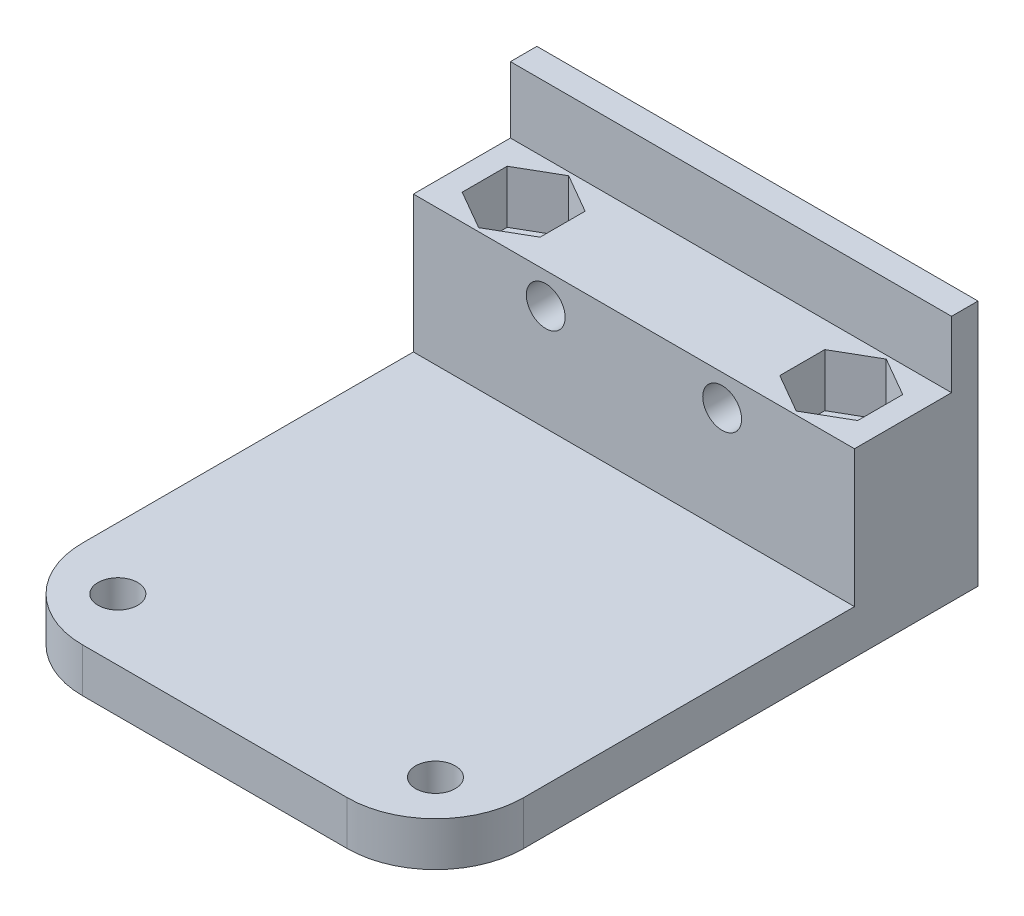
SolidWorks part; units mm, degrees
ref_plane "Front Plane" through (0, 0, 0) normal (0, 0, 1) x (1, 0, 0)
ref_plane "Top Plane" through (0, 0, 0) normal (0, 1, 0) x (1, 0, 0)
ref_plane "Right Plane" through (0, 0, 0) normal (1, 0, 0) x (0, 0, -1)
sketch "Sketch1" plane through (0, 0, 0) normal (0, 0, 1) x (1, 0, 0)
  line L1 (-25, 16.5) -> (25, 16.5)
  line L2 (-25, 16.5) -> (-25, -16.5)
  line L3 (-25, -16.5) -> (25, -16.5)
  line L4 (25, 16.5) -> (25, -16.5)
  line L5 (-25, 16.5) -> (25, -16.5) construction
  line L6 (-25, -16.5) -> (25, 16.5) construction
  point P0 (0, 0)
  dimension "D1" = 33
  dimension "D2" = 50
extrude "Boss-Extrude1" add sketch "Sketch1" along normal blind 3 contours L2 L3 L4 L1
sketch "Sketch2" plane through (0, 0, 3) normal (0, 0, 1) x (1, 0, 0)
  line L0 (25, 16.5) -> (25, -16.5) construction
  line L1 (-25, -16.5) -> (25, -16.5)
  line L2 (-25, -16.5) -> (-25, -11.5)
  line L3 (-25, -11.5) -> (25, -11.5)
  line L4 (25, -16.5) -> (25, -11.5)
  dimension "D1" = 5
extrude "Boss-Extrude2" add sketch "Sketch2" along normal blind 58.5
sketch "Sketch6" plane through (0, 0, 3) normal (0, 0, 1) x (1, 0, 0)
  line L0 (25, 16.5) -> (25, -11.5) construction
  line L1 (-25, 16.5) -> (25, 16.5)
  line L2 (-25, 16.5) -> (-25, 11.5)
  line L3 (-25, 11.5) -> (25, 11.5)
  line L4 (25, 16.5) -> (25, 11.5)
  dimension "D1" = 5
extrude "Cut-Extrude3" cut sketch "Sketch6" against normal up to surface (3 mm away) up to face at (0, 0, 0)
sketch "Sketch7" plane through (0, -11.5, 0) normal (0, 1, 0) x (1, 0, 0)
  line L0 (25, -61.5) -> (25, -3) construction
  line L1 (-25, -3) -> (25, -3)
  line L2 (-25, -3) -> (-25, -14)
  line L3 (-25, -14) -> (25, -14)
  line L4 (25, -3) -> (25, -14)
  dimension "D1" = 11
extrude "Boss-Extrude4" add sketch "Sketch7" along normal blind 15.5
sketch "Sketch8" plane through (0, 4, 0) normal (0, 1, 0) x (1, 0, 0)
  line L1 (-18, -3.4) -> (-22.4167, -5.95)
  line L2 (-22.4167, -5.95) -> (-22.4167, -11.05)
  line L3 (-22.4167, -11.05) -> (-18, -13.6)
  line L4 (-18, -13.6) -> (-13.5833, -11.05)
  line L5 (-13.5833, -11.05) -> (-13.5833, -5.95)
  line L6 (-13.5833, -5.95) -> (-18, -3.4)
  line L8 (0, -15.4) -> (0, 15.4) construction
  line L9 (13.5833, -5.95) -> (18, -3.4)
  line L10 (13.5833, -11.05) -> (13.5833, -5.95)
  line L11 (18, -13.6) -> (13.5833, -11.05)
  line L12 (22.4167, -11.05) -> (18, -13.6)
  line L13 (22.4167, -5.95) -> (22.4167, -11.05)
  line L14 (18, -3.4) -> (22.4167, -5.95)
  circle A1 centre (-18, -8.5) radius 2.2479 construction
  circle A2 centre (-18, -8.5) radius 4.4167 construction
  circle A3 centre (18, -8.5) radius 4.4167 construction
  circle A4 centre (18, -8.5) radius 2.2479 construction
  dimension "D1" = 5.1
extrude "Cut-Extrude4" cut sketch "Sketch8" against normal blind 6
sketch "Sketch4" plane through (0, 0, 3) normal (0, 0, 1) x (1, 0, 0)
  circle A0 centre (-10.0006, 0.5) radius 2.2 construction
  circle A1 centre (-10.0006, 0.5) radius 2.2
  circle A2 centre (9.9994, 0.5) radius 2.2 construction
  circle A3 centre (9.9994, 0.5) radius 2.2
extrude "Cut-Extrude5" cut sketch "Sketch4" along normal through all
sketch "Sketch3" plane through (0, -11.5, 0) normal (0, 1, 0) x (1, 0, 0)
  line L0 (-25, -51.5) -> (-25, -61.5)
  line L1 (-25, -61.5) -> (-15, -61.5)
  line L2 (15, -61.5) -> (25, -61.5)
  line L3 (25, -61.5) -> (25, -51.5)
  arc A1 (15, -61.5) -> (25, -51.5) centre (15, -51.5) ccw construction
  arc A2 (15, -61.5) -> (25, -51.5) centre (15, -51.5) ccw
  arc A3 (-25, -51.5) -> (-15, -61.5) centre (-15, -51.5) ccw construction
  arc A4 (-25, -51.5) -> (-15, -61.5) centre (-15, -51.5) ccw
  circle A5 centre (-18, -54.5) radius 2.2479 construction
  circle A6 centre (-18, -54.5) radius 2.2479
  circle A7 centre (18, -54.5) radius 2.2479 construction
  circle A8 centre (18, -54.5) radius 2.2479
  circle A9 centre (-18, -8.5) radius 2.2479 construction
  circle A10 centre (-18, -8.5) radius 2.2479
  circle A11 centre (18, -8.5) radius 2.2479 construction
  circle A12 centre (18, -8.5) radius 2.2479
extrude "Cut-Extrude1" cut sketch "Sketch3" against normal through all both and the other way through all
